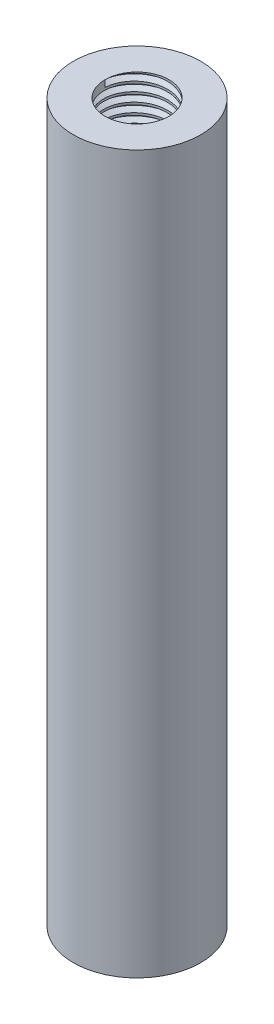
SolidWorks part; units mm, degrees
ref_plane "Front Plane" through (0, 0, 0) normal (0, 0, 1) x (1, 0, 0)
ref_plane "Top Plane" through (0, 0, 0) normal (0, 1, 0) x (1, 0, 0)
ref_plane "Right Plane" through (0, 0, 0) normal (1, 0, 0) x (0, 0, -1)
sketch "Sketch1" plane through (0, 0, 0) normal (0, 1, 0) x (1, 0, 0)
  circle A0 centre (0, 0) radius 3.175
  dimension "D1" = 6.35
extrude "Boss-Extrude1" add sketch "Sketch1" along normal blind 35.7251
sketch "Sketch4" plane through (0, 35.7251, 0) normal (0, 1, 0) x (1, 0, 0)
  circle A0 centre (0, 0) radius 1.5875
  dimension "D1" = 3.175
sketch "Sketch5" plane through (0, 0, 0) normal (0, -1, 0) x (1, 0, 0)
  circle A0 centre (0, 0) radius 1.5875
  dimension "D1" = 3.175
extrude "Cut-Extrude1" cut sketch "Sketch5" against normal blind 6.35
extrude "Cut-Extrude2" cut sketch "Sketch4" against normal blind 6.35
thread "Thread1" pitch 0.7937 method cut profile "Thread Profile1" start angle 0, offset 0, length 0, pitch 0.7937, diameter 3.175
ref_plane "Plane3" through (1.5875, 0, 0) normal (0, 0, 1) x (1, 0, 0)
sketch "Thread Profile1" plane through (1.5875, 0, 0) normal (0, 0, 1) x (1, 0, 0)
  line L0 (0, 0) -> (0, 0.7937) construction
  line L1 (0, 0) -> (0.4296, 0.248)
  line L2 (0.4296, 0.248) -> (0.4296, 0.3473)
  line L3 (0.4296, 0.3473) -> (0, 0.5953)
  line L4 (0.4296, 0.2977) -> (0, 0.2977) construction
  line L11 (0, 0) -> (0, 0.5953)
  point P2 (0, 0)
  dimension "Pitch" = 0.7937
  dimension "Profile_Angle" = 60
  dimension "Profile_Land" = 0.0992
  dimension "Profile_Height" = 0.4296
thread "Thread2" pitch 0.4536 method cut profile "Thread Profile2" start angle 0, offset 0, length 0, pitch 0.4536, diameter 3.175
ref_plane "Plane4" through (-1.5875, 35.7251, 0) normal (0, 0, 1) x (-1, 0, 0)
sketch "Thread Profile2" plane through (-1.5875, 35.7251, 0) normal (0, 0, 1) x (-1, 0, 0)
  line L0 (0, 0) -> (0, 0.4536) construction
  line L1 (0, 0) -> (0.2455, 0.1417)
  line L2 (0.2455, 0.1417) -> (0.2455, 0.1984)
  line L3 (0.2455, 0.1984) -> (0, 0.3402)
  line L4 (0.2455, 0.1701) -> (0, 0.1701) construction
  line L11 (0, 0) -> (0, 0.3402)
  point P2 (0, 0)
  dimension "Pitch" = 0.4536
  dimension "Profile_Angle" = 60
  dimension "Profile_Land" = 0.0567
  dimension "Profile_Height" = 0.2455
